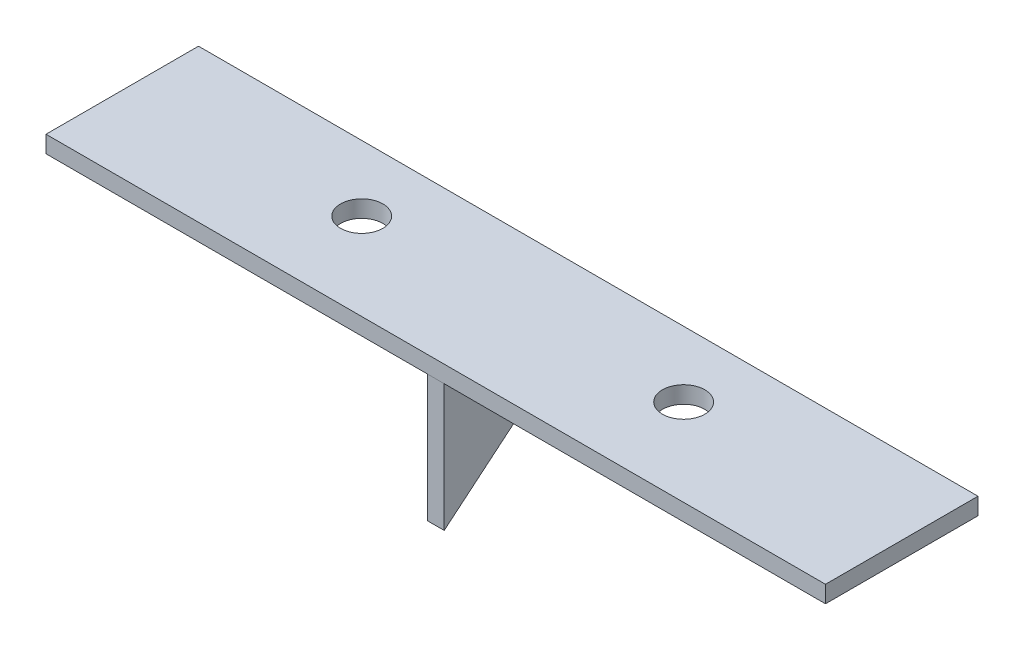
SolidWorks part; units mm, degrees
note: The reader was unsure of these and kept them because the rebuilt part matched: thickness of "Base-Flange1", "Sheet-Metal1", "Sheet-Metal3".
material "1023 Carbon Steel Sheet (SS)"
ref_plane "Front Plane" through (0, 0, 0) normal (0, 0, 1) x (1, 0, 0)
ref_plane "Top Plane" through (0, 0, 0) normal (0, 1, 0) x (1, 0, 0)
ref_plane "Right Plane" through (0, 0, 0) normal (1, 0, 0) x (0, 0, -1)
sketch "Sketch1" plane through (0, 0, 0) normal (0, 1, 0) x (1, 0, 0)
  line L0 (-46, 18) -> (-46, 0)
  line L1 (-46, 18) -> (46, 18)
  line L2 (-46, 0) -> (46, 0)
  line L3 (46, 18) -> (46, 0)
  line L4 (-46, 18) -> (46, 0) construction
  line L5 (-46, 0) -> (46, 18) construction
  point P1 (0, 9)
  dimension "D1" = 92
  dimension "D2" = 18
base flange "Base-Flange1" sketch "Sketch1" thickness 2 reverse thickness direction no parameters "D1"=0.7366
sketch "Sketch11" plane through (0, 0, 0) normal (0, 1, 0) x (1, 0, 0)
  line L1 (0, 0) -> (0, 28.0708) construction
  line L2 (-46, 0) -> (46, 0) construction
  circle A0 centre (-19, 10.26) radius 2.5
  circle A1 centre (19, 10.26) radius 2.5
  dimension "D2" = 5
  dimension "D1" = 10.26
  dimension "D3" = 19
extrude "Cut-Extrude1" cut sketch "Sketch11" against normal blind 10 normal cut yes
sketch "Sketch12" plane through (0, 0, 0) normal (1, 0, 0) x (0, 0, -1)
  line L0 (18, -2) -> (0, -17)
  line L1 (0, -17) -> (0, -2)
  line L2 (0, -2) -> (18, -2)
  dimension "D1" = 15
extrude "Boss-Extrude1" add sketch "Sketch12" along normal mid plane 2 separate body
sketch "Bend-Lines1" [suppressed] plane through (0, 0, 0) normal (0, 1, 0) x (1, 0, 0)
sketch "Bounding-Box1" [suppressed] plane through (0, 0, 0) normal (0, 1, 0) x (1, 0, 0)
sheet metal parameters "Sheet-Metal1" thickness 2 parameters "D1"=0.7366
flat pattern "Flat-Pattern1" [suppressed]
sketch "Bend-Lines2" plane through (0, 0, 0) normal (0, 1, 0) x (1, 0, 0)
sketch3d "Bounding-Box2" [suppressed]
  line L0 (-232, 18, 0) -> (232, 18, 0) construction
  line L1 (-232, 0, 0) -> (232, 0, 0) construction
  line L2 (-232, 18, 0) -> (-232, 0, 0) construction
  line L3 (232, 18, 0) -> (232, 0, 0) construction
sheet metal parameters "Sheet-Metal3" thickness 2 parameters "D1"=0.7366, "D7"=1
flat pattern "Flat-Pattern1"
sketch "Bend-Lines2" plane through (0, 0, 0) normal (0, 1, 0) x (1, 0, 0)
sketch3d "Bounding-Box2" [suppressed]
  line L0 (46, 18, 0) -> (-46, 18, 0) construction
  line L1 (46, 0, 0) -> (-46, 0, 0) construction
  line L2 (46, 18, 0) -> (46, 0, 0) construction
  line L3 (-46, 18, 0) -> (-46, 0, 0) construction
